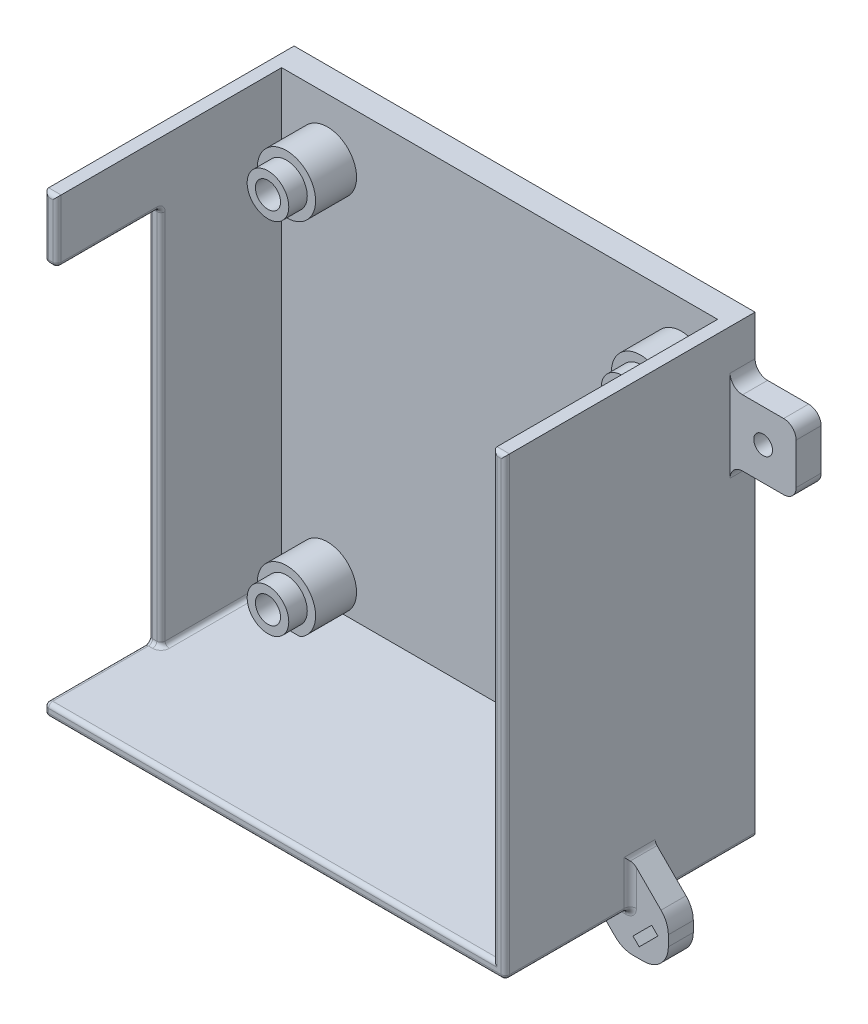
SolidWorks part; units mm, degrees
material "ABS"
ref_plane "X-Y Datum" through (0, 0, 0) normal (0, 0, 1) x (1, 0, 0)
ref_plane "X-Z Datum" through (0, 0, 0) normal (0, 1, 0) x (1, 0, 0)
ref_plane "Y-Z Datum" through (0, 0, 0) normal (1, 0, 0) x (0, 0, -1)
sketch "Sketch1" plane through (0, 0, 0) normal (0, 0, 1) x (1, 0, 0)
  line L1 (-52.3875, 53.1812) -> (52.3875, 53.1812)
  line L2 (-52.3875, 53.1812) -> (-52.3875, -53.1812)
  line L3 (-52.3875, -53.1812) -> (52.3875, -53.1812)
  line L4 (52.3875, 53.1812) -> (52.3875, -53.1812)
  line L5 (-52.3875, 53.1812) -> (52.3875, -53.1812) construction
  line L6 (-52.3875, -53.1812) -> (52.3875, 53.1812) construction
  point P0 (0, 0)
  dimension "D1" = 104.775
  dimension "D2" = 106.3625
extrude "Boss-Extrude1" add sketch "Sketch1" along normal blind 6
sketch "Sketch2" plane through (0, 0, 0) normal (0, 0, 1) x (1, 0, 0)
  line L1 (-55.3875, -53.1812) -> (-55.3875, -56.1812)
  line L2 (-55.3875, 53.1812) -> (-55.3875, -53.1812)
  line L4 (55.3875, 53.1812) -> (52.3875, 53.1812)
  line L5 (55.3875, -56.1812) -> (55.3875, 53.1812)
  line L6 (-52.3875, -56.1812) -> (55.3875, -56.1812)
  line L7 (55.3875, -56.1812) -> (55.3875, 53.1812)
  line L8 (-52.3875, -56.1812) -> (55.3875, -56.1812)
  line L9 (52.3875, -53.1812) -> (52.3875, 53.1812) construction
  line L10 (-52.3875, -53.1812) -> (52.3875, -53.1812) construction
  line L11 (52.3875, -53.1812) -> (52.3875, 53.1812)
  line L12 (-52.3875, -53.1812) -> (52.3875, -53.1812)
  line L13 (-55.3875, 53.1812) -> (-55.3875, -53.1812)
  line L14 (-55.3875, -56.1812) -> (-52.3875, -56.1812)
  line L15 (-55.3875, 53.1812) -> (-52.3875, 53.1812)
  line L16 (-52.3875, 53.1812) -> (-52.3875, -53.1812) construction
  line L17 (-52.3875, 53.1812) -> (-52.3875, -53.1812)
  dimension "D1" = 3
  dimension "D2" = 3
extrude "Boss-Extrude2" add sketch "Sketch2" along normal blind 35
sketch "Sketch3" plane through (0, 0, 6) normal (0, 0, 1) x (1, 0, 0)
  circle A0 centre (-41.382, 39.351) radius 3.025
  circle A1 centre (43.708, 39.351) radius 3.025
  circle A2 centre (43.708, -47.009) radius 3.025
  circle A3 centre (-41.382, -47.009) radius 3.025
  circle A4 centre (43.708, 39.351) radius 5
  circle A5 centre (-41.382, 39.351) radius 5
  circle A6 centre (-41.382, -47.009) radius 5
  circle A7 centre (43.708, -47.009) radius 5
  point P0 (-41.382, 39.351)
  point P1 (-41.382, -47.009)
  point P3 (43.708, -47.009)
  point P5 (43.708, 39.351)
  dimension "D1" = 6.05
  dimension "D2" = 10
extrude "Boss-Extrude3" add sketch "Sketch3" along normal blind 14.2875
sketch "Sketch4" plane through (0, 0, 6) normal (0, 0, 1) x (1, 0, 0)
  circle A0 centre (43.708, 39.351) radius 7
  circle A1 centre (-41.382, 39.351) radius 7
  circle A2 centre (-41.382, -47.009) radius 7
  circle A3 centre (43.708, -47.009) radius 7
  circle A5 centre (-41.382, -47.009) radius 3.025
  circle A6 centre (-41.382, -47.009) radius 3.025
  circle A7 centre (43.708, -47.009) radius 3.025
  circle A8 centre (43.708, -47.009) radius 3.025
  circle A9 centre (43.708, 39.351) radius 3.025
  circle A10 centre (43.708, 39.351) radius 3.025
  circle A11 centre (-41.382, 39.351) radius 3.025
  circle A12 centre (-41.382, 39.351) radius 3.025
  dimension "D1" = 14
  dimension "D2" = 0
  dimension "D3" = 0
  dimension "D4" = 0
  dimension "D5" = 0
extrude "Boss-Extrude4" add sketch "Sketch4" along normal blind 9.8425
sketch "Sketch6" plane through (0, 0, 0) normal (0, 0, 1) x (1, 0, 0)
  line L0 (-71.2675, -40.3012) -> (-55.3875, -56.1812) construction
  line L5 (55.3875, -56.1812) -> (55.3875, 53.1812) construction
  line L6 (55.3875, 40.4812) -> (71.2625, 40.4812)
  line L7 (55.3875, 40.4812) -> (55.3875, 24.6062)
  line L8 (55.3875, 24.6062) -> (71.2625, 24.6062)
  line L9 (71.2625, 40.4812) -> (71.2625, 24.6062)
  line L10 (55.3875, 24.6062) -> (71.2625, 40.4812)
  line L11 (55.3875, 53.1812) -> (52.3875, 53.1812) construction
  line L13 (-55.3875, -56.1812) -> (-71.2675, -56.1812)
  line L14 (-55.3875, -56.1812) -> (-55.3875, -40.3012)
  line L15 (-55.3875, -40.3012) -> (-71.2675, -40.3012)
  line L17 (-71.2675, -56.1812) -> (-71.2675, -40.3012)
  circle A1 centre (63.325, 32.5437) radius 2 construction
  circle A2 centre (-63.3275, -48.2413) radius 2 construction
  dimension "D1" = 15.88
  dimension "D6" = 4
  dimension "D2" = 4
  dimension "D4" = 15.875
  dimension "D5" = 15.875
  dimension "D7" = 12.7
extrude "Boss-Extrude5" add sketch "Sketch6" along normal blind 6 contours L14 L15 | L17 L13 | L10 L8 L9 | L7 L10 L6 region at (60.6792, 35.1896, 0) region at (65.9708, 29.8979, 0) region at (-63.3275, -48.2412, 0)
hole_wizard "M4 Clearance Hole1" positions "Sketch7" profile "Sketch8" hole size "M4" standard "ANSI Metric" end condition through all
sketch "Sketch7" plane through (0, 0, 6) normal (0, 0, 1) x (1, 0, 0)
  point P0 (63.325, 32.5437)
  point P8 (-63.3275, -48.2413)
sketch "Sketch8" plane through (63.325, 32.5437, 6) normal (1, 0, 0) x (0, -1, 0)
  line L0 (0, 0) -> (0, 6)
  line L1 (0, 6) -> (2.25, 6)
  line L2 (2.25, 6) -> (2.25, 0)
  line L5 (2.25, 0) -> (0, 0)
  line L11 (0, -6.35) -> (0, 107.95) construction
  dimension "Thru Hole Dia." = 4.5
  dimension "Thru Hole Depth" = 6
fillet "Fillet2" radius 3 6 edges at (71.2625, 24.6062, 3) (71.2625, 40.4812, 3) (55.3875, 40.4812, 3) (55.3875, 24.6062, 3) (-71.2675, -56.1812, 3) (-71.2675, -40.3012, 3)
sketch "Sketch9" plane through (0, 0, 35) normal (0, 0, 1) x (1, 0, 0)
  line L0 (-52.3875, 38.1812) -> (-55.3875, 38.1812)
  line L1 (-52.3875, -53.1812) -> (-55.3875, -53.1812)
  line L8 (-52.3875, -53.1812) -> (-52.3875, 53.1812)
  line L9 (-52.3875, 53.1812) -> (-55.3875, 53.1812)
  line L10 (-55.3875, 53.1812) -> (-55.3875, -56.1812)
  line L11 (-55.3875, -56.1812) -> (55.3875, -56.1812)
  line L12 (55.3875, -56.1812) -> (55.3875, 53.1812)
  line L13 (55.3875, 53.1812) -> (52.3875, 53.1812)
  line L14 (52.3875, 53.1812) -> (52.3875, -53.1812)
  line L15 (52.3875, -53.1812) -> (-52.3875, -53.1812)
  line L16 (-52.3875, -53.1812) -> (-52.3875, 53.1812)
  line L17 (-52.3875, 53.1812) -> (-55.3875, 53.1812)
  line L18 (-55.3875, 53.1812) -> (-55.3875, -56.1812)
  line L19 (-55.3875, -56.1812) -> (55.3875, -56.1812)
  line L20 (55.3875, -56.1812) -> (55.3875, 53.1812)
  line L21 (55.3875, 53.1812) -> (52.3875, 53.1812)
  line L22 (52.3875, 53.1812) -> (52.3875, -53.1812)
  line L23 (52.3875, -53.1812) -> (-52.3875, -53.1812)
  line M10 (-52.3875, -53.1812) -> (-52.3875, 53.1812)
  line M11 (-52.3875, 53.1812) -> (-55.3875, 53.1812)
  line M12 (-55.3875, 53.1812) -> (-55.3875, -56.1812)
  line M13 (-55.3875, -56.1812) -> (55.3875, -56.1812)
  line M14 (55.3875, -56.1812) -> (55.3875, 53.1812)
  line M15 (55.3875, 53.1812) -> (52.3875, 53.1812)
  line M16 (52.3875, 53.1812) -> (52.3875, -53.1812)
  line M17 (52.3875, -53.1812) -> (-52.3875, -53.1812)
  dimension "D2" = 15
  dimension "D1" = 0
extrude "Boss-Extrude6" add sketch "Sketch9" along normal blind 25 contours L1 M17 M12 M13 M14 M15 M16 | L0 M10 M11 M12 region at (-53.8875, 45.6812, 35) region at (0, -54.7379, 35)
fillet "Fillet3" radius 1 20 edges at (-53.8875, -53.1812, 35) (55.3875, -56.1812, 30) (-55.3875, -7.5, 35) (-52.3875, -7.5, 35) (-52.3875, -53.1812, 20.5) (-55.3875, -56.1812, 33) (-52.3875, 38.1812, 47.5) (-55.3875, -53.1812, 47.5) (-55.3875, 38.1812, 47.5) (-53.8875, 38.1812, 35) (52.3875, 0, 60) (53.8875, 53.1812, 60) (55.3875, -1.5, 60) (0, -56.1812, 60) (-55.3875, -54.6812, 60) (-1.5, -53.1812, 60) (-55.3875, 45.6812, 60) (-53.8875, 53.1812, 60) (-52.3875, 45.6812, 60) (-53.8875, 38.1812, 60)
ref_plane "Plane1" through (0, 0, 30) normal (0, 0, -1) x (-1, 0, 0)
sketch "Sketch10" plane through (0, 0, 30) normal (0, 0, -1) x (-1, 0, 0)
  line L0 (-54.3875, -55.1812) -> (54.3875, -55.1812) construction
  line L1 (54.3875, -55.1812) -> (54.3875, -56.1812) construction
  line L2 (54.3875, -56.1812) -> (-54.3875, -56.1812) construction
  line L3 (-55.3875, -55.1812) -> (-55.3875, 53.1812) construction
  line L4 (-55.3875, 53.1812) -> (-54.3875, 52.1812) construction
  line L5 (-54.3875, 52.1812) -> (-54.3875, -55.1812) construction
  line L6 (-54.3875, -56.1812) -> (54.3875, -56.1812) construction
  line L7 (-54.3875, -55.1812) -> (54.3875, -55.1812)
  line L8 (54.3875, -55.1812) -> (54.3875, -56.1812)
  line L9 (54.3875, -56.1812) -> (-54.3875, -56.1812)
  line L10 (-55.3875, -55.1812) -> (-55.3875, 53.1812)
  line L11 (-55.3875, 53.1812) -> (-54.3875, 52.1812)
  line L12 (-54.3875, 52.1812) -> (-54.3875, -55.1812)
  line L13 (-54.3875, -56.1812) -> (54.3875, -56.1812)
  line L14 (-53.3875, -54.1812) -> (-59.0444, -59.8381)
  line L15 (-53.5444, -65.3381) -> (-44.3875, -56.1813)
  line L16 (-53.5444, -54.3381) -> (-64.5444, -54.3381)
  line L17 (-53.5444, -54.3381) -> (-53.5444, -65.3381)
  line L18 (-53.5444, -65.3381) -> (-64.5444, -65.3381)
  line L19 (-64.5444, -54.3381) -> (-64.5444, -65.3381)
  line L20 (-53.5444, -54.3381) -> (-64.5444, -65.3381) construction
  line L21 (-53.5444, -65.3381) -> (-64.5444, -54.3381) construction
  line L26 (-62.0444, -58.3381) -> (-60.5444, -56.8381)
  line L27 (-56.0444, -58.3381) -> (-62.0444, -58.3381)
  line L28 (-64.5444, -54.3381) -> (-55.3875, -45.1813)
  line L29 (-56.0444, -58.3381) -> (-56.0444, -61.3381)
  line L30 (-56.0444, -61.3381) -> (-62.0444, -61.3381)
  line L31 (-62.0444, -58.3381) -> (-62.0444, -61.3381)
  line L32 (-56.0444, -58.3381) -> (-62.0444, -61.3381) construction
  line L33 (-56.0444, -61.3381) -> (-62.0444, -58.3381) construction
  line L34 (-57.5444, -56.8381) -> (-60.5444, -56.8381)
  line L35 (-57.5444, -56.8381) -> (-57.5444, -62.8381)
  line L36 (-57.5444, -62.8381) -> (-60.5444, -62.8381)
  line L37 (-60.5444, -56.8381) -> (-60.5444, -62.8381)
  line L38 (-57.5444, -56.8381) -> (-60.5444, -62.8381) construction
  line L39 (-57.5444, -62.8381) -> (-60.5444, -56.8381) construction
  line L40 (-57.5444, -62.8381) -> (-56.0444, -61.3381)
  line L41 (-56.0444, -61.3381) -> (-60.5444, -56.8381)
  line L42 (-57.5444, -62.8381) -> (-62.0444, -58.3381)
  arc A0 (-55.3875, -55.1812) -> (-54.3875, -56.1812) centre (-54.3875, -55.1812) ccw construction
  arc A1 (-55.3875, -55.1812) -> (-54.3875, -56.1812) centre (-54.3875, -55.1812) ccw
  dimension "D1" = 3
  dimension "D2" = 11
  dimension "D3" = 11
  dimension "D4" = 45
  dimension "D5" = 45
  dimension "D6" = 6
  dimension "D7" = 8
  dimension "D8" = 3
  dimension "D9" = 6
  dimension "D10" = 6.364
extrude "Boss-Extrude7" add sketch "Sketch10" along normal blind 6 contours A1 L10 L16 L19 L18 L17 L9 L27 L29 L40 L36 L37 L30 L31 L26 L34 L35 | L36 L42 L30 L37 | L30 L42 L37 | L37 L42 L31 L30 | L41 L27 L35 L34 | L41 L29 L27 L35 | L41 L14 L27 | L41 L35 L14 | L13 L17 L15 | L28 L16 L10 region at (56.711, -59.5048, 30) region at (57.7944, -59.0881, 30) region at (58.2944, -58.5881, 30) region at (58.711, -57.5048, 30) region at (54.8297, -56.2489, 30) region at (50.4921, -59.2335, 30) region at (58.4398, -51.2858, 30) region at (59.3777, -62.1714, 30) region at (61.3777, -60.1714, 30) region at (60.0444, -60.8381, 30)
fillet "Fillet4" radius 6 3 edges at (64.5444, -54.3381, 27) (64.5444, -65.3381, 27) (53.5444, -65.3381, 27)
fillet "Fillet5" radius 1.5 5 edges at (55.3875, -50.1813, 30) (55.0946, -55.8884, 30) (55.3875, -45.1813, 27) (44.3875, -56.1812, 27) (49.3875, -56.1812, 30)
